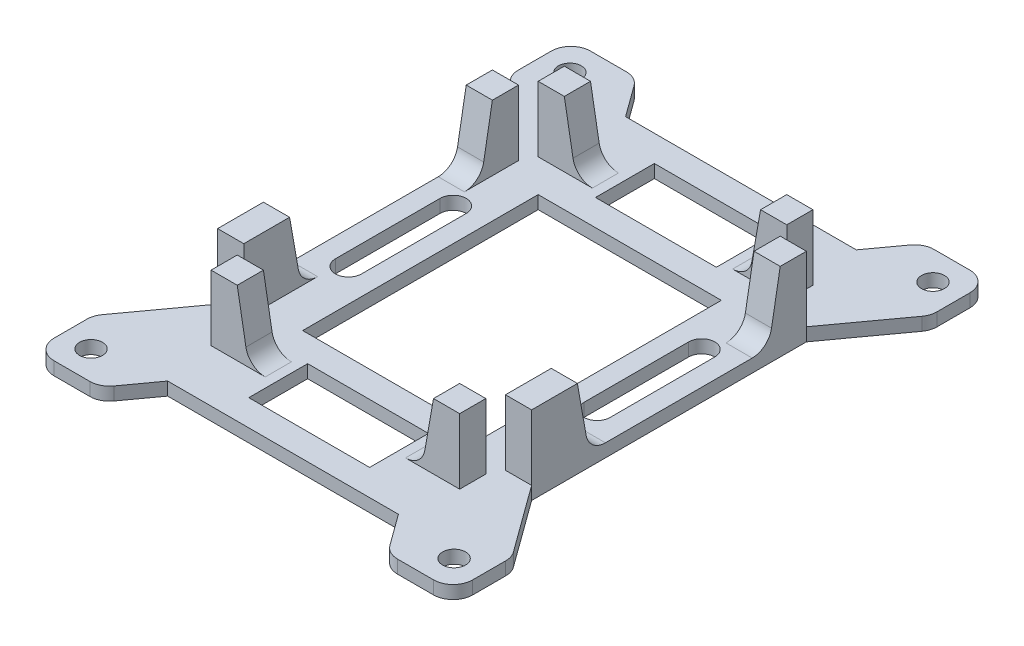
SolidWorks part; units mm, degrees
ref_plane "Front Plane" through (0, 0, 0) normal (0, 0, 1) x (1, 0, 0)
ref_plane "Top Plane" through (0, 0, 0) normal (0, 1, 0) x (1, 0, 0)
ref_plane "Right Plane" through (0, 0, 0) normal (1, 0, 0) x (0, 0, -1)
sketch "Sketch1" plane through (0, 0, 0) normal (0, 1, 0) x (1, 0, 0)
  line L0 (-32, 0) -> (32, 0) construction
  line L1 (-32, 41) -> (32, 41)
  line L2 (-32, 41) -> (-32, -41)
  line L3 (-32, -41) -> (32, -41)
  line L4 (32, 41) -> (32, -41)
  line L5 (-32, 41) -> (32, -41) construction
  line L6 (-32, -41) -> (32, 41) construction
  line L7 (0, 41) -> (0, -41) construction
  line L9 (-14, 18) -> (14, 18)
  line L10 (-14, 18) -> (-14, -18)
  line L11 (-14, -18) -> (14, -18)
  line L12 (14, 18) -> (14, -18)
  line L13 (-14, 18) -> (14, -18) construction
  line L14 (-14, -18) -> (14, 18) construction
  circle A0 centre (27.75, -36.6) radius 1.75
  circle A1 centre (-27.75, -36.6) radius 1.75
  circle A2 centre (-27.75, 36.6) radius 1.75
  circle A3 centre (27.75, 36.6) radius 1.75
  point P0 (0, 0)
  point P18 (0, 0)
  dimension "D3" = 3.5
  dimension "D1" = 82
  dimension "D2" = 64
  dimension "D4" = 27.75
  dimension "D5" = 36.6
  dimension "D6" = 28
  dimension "D7" = 36
extrude "Boss-Extrude1" add sketch "Sketch1" along normal blind 2
sketch "Sketch4" plane through (0, 2, 0) normal (0, 1, 0) x (1, 0, 0)
  line L0 (-32, 0) -> (32, 0) construction
  line L1 (-32, 41) -> (-32, -41) construction
  line L2 (32, -41) -> (32, 41) construction
  line L3 (0, 41) -> (0, -41) construction
  line L4 (32, 41) -> (-32, 41) construction
  line L5 (-32, -41) -> (32, -41) construction
  line L6 (-15, -23) -> (-15, -27)
  line L7 (-20, 23) -> (20, 23) construction
  line L8 (-20, 23) -> (-20, -23) construction
  line L9 (-20, -23) -> (20, -23) construction
  line L10 (20, 23) -> (20, -23) construction
  line L11 (-20, 23) -> (20, -23) construction
  line L12 (-20, -23) -> (20, 23) construction
  line L13 (19, -23) -> (15, -23)
  line L14 (19, -23) -> (19, -27)
  line L15 (19, -27) -> (15, -27)
  line L16 (15, -23) -> (15, -27)
  line L17 (-19, -27) -> (-15, -27)
  line L18 (-19, -23) -> (-19, -27)
  line L19 (-19, -23) -> (-15, -23)
  line L20 (-19, 23) -> (-15, 23)
  line L21 (-19, 23) -> (-19, 27)
  line L22 (-19, 27) -> (-15, 27)
  line L23 (15, 23) -> (15, 27)
  line L24 (19, 27) -> (15, 27)
  line L25 (19, 23) -> (19, 27)
  line L26 (19, 23) -> (15, 23)
  line L27 (-15, 23) -> (-15, 27)
  line L28 (-24, -21) -> (-24, -14)
  line L29 (20, -21) -> (24, -21)
  line L30 (20, -21) -> (20, -14)
  line L31 (20, -14) -> (24, -14)
  line L32 (24, -21) -> (24, -14)
  line L33 (-20, -21) -> (-24, -21)
  line L34 (-20, -14) -> (-24, -14)
  line L35 (-20, -21) -> (-20, -14)
  line L36 (-24, 21) -> (-24, 17)
  line L37 (20, 21) -> (24, 21)
  line L38 (20, 21) -> (20, 17)
  line L39 (20, 17) -> (24, 17)
  line L40 (24, 21) -> (24, 17)
  line L41 (-20, 17) -> (-24, 17)
  line L42 (-20, 21) -> (-24, 21)
  line L43 (-20, 21) -> (-20, 17)
  point P12 (0, 0)
  dimension "D1" = 46
  dimension "D2" = 40
  dimension "D3" = 1
  dimension "D4" = 4
  dimension "D5" = 4
  dimension "D6" = 2
  dimension "D7" = 4
  dimension "D8" = 7
  dimension "D9" = 2
  dimension "D10" = 4
  dimension "D11" = 4
extrude "Boss-Extrude2" add sketch "Sketch4" along normal blind 10
sketch "Sketch5" plane through (0, 2, 0) normal (0, 1, 0) x (1, 0, 0)
  line L0 (-32, 32) -> (-24, 21)
  line L1 (-32, 41) -> (-32, -41) construction
  line L2 (-32, 0) -> (32, 0) construction
  line L3 (32, -41) -> (32, 41) construction
  line L4 (-24, 21) -> (-24, -21)
  line L5 (-32, 32) -> (-32, -32)
  line L6 (-32, -32) -> (-24, -21)
  line L7 (0, 41) -> (0, -41) construction
  line L8 (32, 41) -> (-32, 41) construction
  line L9 (-32, -41) -> (32, -41) construction
  line L10 (32, -32) -> (24, -21)
  line L11 (32, 32) -> (32, -32)
  line L12 (24, 21) -> (24, -21)
  line L13 (32, 32) -> (24, 21)
  point P13 (-24, 0)
  point P23 (24, 0)
  dimension "D1" = 32
extrude "Cut-Extrude1" cut sketch "Sketch5" against normal through all
draft "Draft12" type of draft neutral plane draft angle 10 faces to draft 4 face at (22, 7, 14) face at (22, 7, -17) face at (-22, 7, 14) face at (-22, 7, -17) neutral plane through (0, 12, 0) neutral plane normal (0, 1, 0) parameters "D1"=10
draft "Draft13" type of draft neutral plane draft angle 10 faces to draft 4 face at (15, 7, 25) face at (-15, 7, 25) face at (15, 7, -25) face at (-15, 7, -25) neutral plane through (0, 12, 0) neutral plane normal (0, 1, 0) parameters "D1"=10
sketch "Sketch6" plane through (0, 2, 0) normal (0, 1, 0) x (1, 0, 0)
  line L0 (0, 41) -> (0, -41) construction
  line L1 (32, 41) -> (-32, 41) construction
  line L2 (-32, -41) -> (32, -41) construction
  line L3 (-22, 41) -> (-17.6364, 35)
  line L4 (-17.6364, 35) -> (17.6364, 35)
  line L5 (-22, 41) -> (22, 41)
  line L6 (-24, 21) -> (-32, 32) construction
  line L7 (22, 41) -> (17.6364, 35)
  line L8 (-24, 0) -> (24, 0) construction
  line L9 (19, 10) -> (19, -6) construction
  line L10 (17, 10) -> (17, -6)
  line L11 (-24, -12.2367) -> (-24, 15.2367) construction
  line L12 (24, 15.2367) -> (24, -12.2367) construction
  line L13 (22, -41) -> (17.6364, -35)
  line L14 (21, 10) -> (21, -6)
  line L15 (-22, -41) -> (22, -41)
  line L16 (-17.6364, -35) -> (17.6364, -35)
  line L17 (-22, -41) -> (-17.6364, -35)
  line L18 (14, 18) -> (-14, 18) construction
  line L19 (-9.2367, 31) -> (9.2367, 31)
  line L20 (-9.2367, 31) -> (-9.2367, 22)
  line L21 (-9.2367, 22) -> (9.2367, 22)
  line L22 (9.2367, 31) -> (9.2367, 22)
  line L23 (-9.2367, 31) -> (9.2367, 22) construction
  line L24 (-9.2367, 22) -> (9.2367, 31) construction
  line L25 (13.2367, 27) -> (13.2367, 23) construction
  line L27 (9.2367, -31) -> (9.2367, -22)
  line L28 (-9.2367, -22) -> (9.2367, -22)
  line L29 (-9.2367, -31) -> (-9.2367, -22)
  line L30 (-9.2367, -31) -> (9.2367, -31)
  line L31 (-19, 10) -> (-19, -6) construction
  line L32 (-17, 10) -> (-17, -6)
  line L33 (-21, 10) -> (-21, -6)
  line L34 (-14, 18) -> (-14, -18) construction
  arc A0 (-17, 10) -> (-21, 10) centre (-19, 10) ccw
  arc A1 (-21, -6) -> (-17, -6) centre (-19, -6) ccw
  arc A2 (17, 10) -> (21, 10) centre (19, 10) cw
  arc A3 (21, -6) -> (17, -6) centre (19, -6) cw
  point P13 (0, 35)
  point P26 (0, 26.5)
  point P41 (-19, 2)
  point P50 (19, 2)
  dimension "D1" = 6
  dimension "D2" = 22
  dimension "D3" = 4
  dimension "D4" = 4
  dimension "D5" = 4
  dimension "D6" = 3
  dimension "D7" = 3
  dimension "D8" = 6
  dimension "D9" = 10
extrude "Cut-Extrude2" cut sketch "Sketch6" against normal through all
fillet "Fillet1" radius 3 12 edges at (-22, 1, -41) (22, 1, -41) (32, 1, -41) (32, 1, -32) (32, 1, 32) (32, 1, 41) (22, 1, 41) (-22, 1, 41) (-32, 1, 41) (-32, 1, 32) (-32, 1, -32) (-32, 1, -41)
fillet "Fillet2" radius 3 8 edges at (-13.2367, 2, -25) (13.2367, 2, -25) (22, 2, -15.2367) (22, 2, 12.2367) (13.2367, 2, 25) (-13.2367, 2, 25) (-22, 2, 12.2367) (-22, 2, -15.2367)
